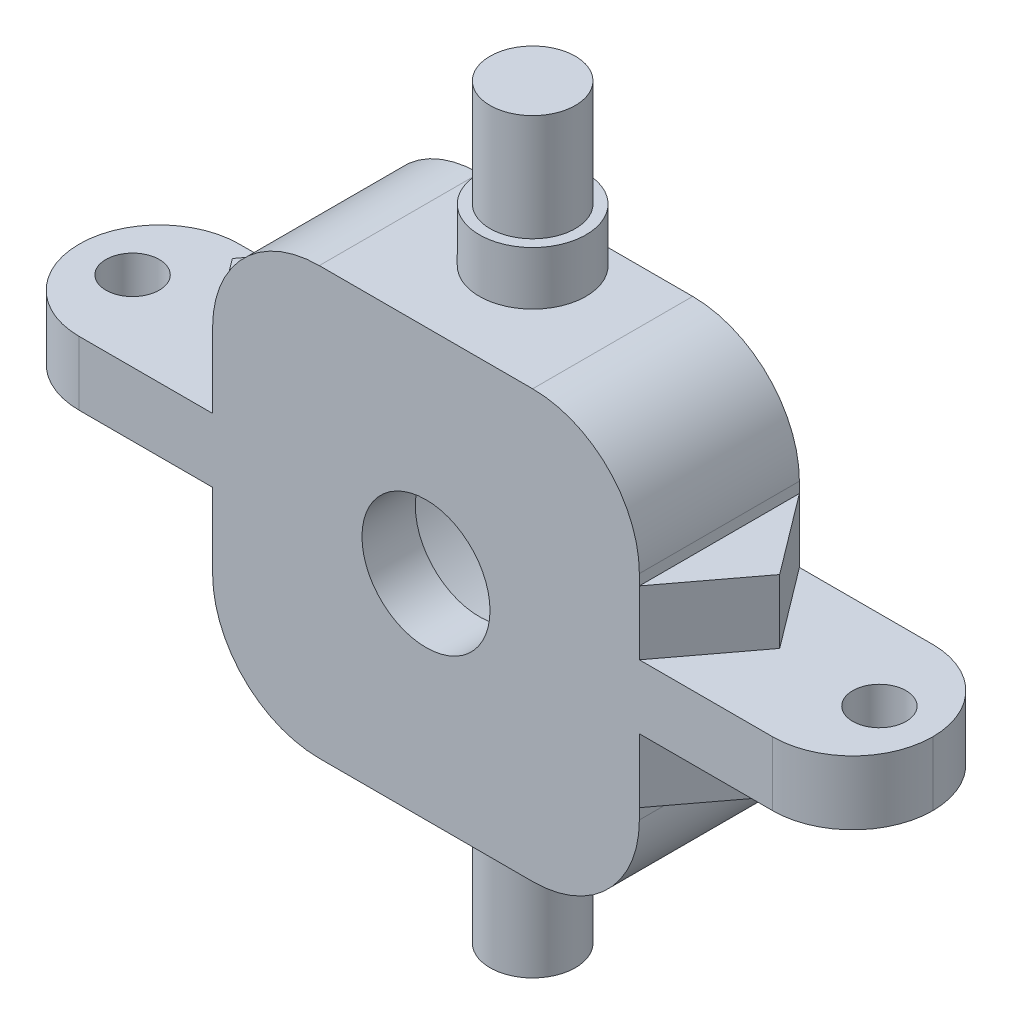
SolidWorks part; units mm, degrees
ref_plane "Front Plane" through (0, 0, 0) normal (0, 0, 1) x (1, 0, 0)
ref_plane "Top Plane" through (0, 0, 0) normal (0, 1, 0) x (1, 0, 0)
ref_plane "Right Plane" through (0, 0, 0) normal (1, 0, 0) x (0, 0, -1)
sketch "Sketch1" plane through (0, 0, 0) normal (0, 0, 1) x (1, 0, 0)
  line L1 (40, 40) -> (0, 40)
  line L2 (40, 40) -> (40, 0)
  line L3 (40, 0) -> (0, 0)
  line L4 (0, 40) -> (0, 0)
  circle A0 centre (20, 20) radius 6
  dimension "D3" = 12
  dimension "D1" = 40
  dimension "D2" = 40
extrude "Boss-Extrude1" add sketch "Sketch1" along normal blind 15
sketch "Sketch2" plane through (0, 0, 0) normal (0, 0, -1) x (-1, 0, 0)
  circle A0 centre (-20, 20) radius 15
  dimension "D1" = 30
extrude "Cut-Extrude1" cut sketch "Sketch2" against normal blind 10
sketch "Sketch4" plane through (0, 40, 0) normal (0, 1, 0) x (1, 0, 0)
  line L0 (40, 0) -> (0, 0) construction
  circle A0 centre (20, -5) radius 4
  dimension "D1" = 8
  dimension "D2" = 5
extrude "Boss-Extrude2" add sketch "Sketch4" along normal blind 15
sketch "Sketch5" plane through (0, 40, 0) normal (0, 1, 0) x (1, 0, 0)
  circle A0 centre (20, -5) radius 5
extrude "Boss-Extrude3" add sketch "Sketch5" along normal blind 5
sketch "Sketch7" plane through (0, 0, 0) normal (0, -1, 0) x (1, 0, 0)
  line L0 (0, 0) -> (40, 0) construction
  circle A0 centre (20, 5) radius 5
  dimension "D1" = 5
extrude "Boss-Extrude4" add sketch "Sketch7" along normal blind 5
sketch "Sketch8" plane through (0, -5, 0) normal (0, -1, 0) x (1, 0, 0)
  circle A0 centre (20, 5) radius 4
extrude "Boss-Extrude5" add sketch "Sketch8" along normal blind 10
fillet "Fillet1" radius 10 4 edges at (0, 40, 7.5) (0, 0, 7.5) (40, 0, 7.5) (40, 40, 7.5)
sketch "Sketch9" plane through (40, 0, 0) normal (1, 0, 0) x (0, 0, -1)
  line L0 (-15, 20) -> (0, 20) construction
  line L1 (-15, 10) -> (-15, 30) construction
  line L2 (0, 10) -> (0, 30) construction
  line L4 (-15, 17) -> (0, 17)
  line L5 (-15, 17) -> (-15, 23)
  line L6 (-15, 23) -> (0, 23)
  line L7 (0, 17) -> (0, 23)
  line L8 (-15, 17) -> (0, 23) construction
  line L9 (-15, 23) -> (0, 17) construction
  point P6 (-7.5, 20)
  dimension "D1" = 6
extrude "Boss-Extrude6" add sketch "Sketch9" along normal blind 20
sketch "Sketch10" plane through (0, 0, 0) normal (-1, 0, 0) x (0, 0, 1)
  line L1 (0, 17) -> (15, 17)
  line L2 (0, 17) -> (0, 23)
  line L3 (0, 23) -> (15, 23)
  line L4 (15, 17) -> (15, 23)
extrude "Boss-Extrude7" add sketch "Sketch10" along normal blind 20
sketch "Sketch11" plane through (0, 23, 0) normal (0, 1, 0) x (1, 0, 0)
  line L0 (50, 0) -> (50, -15) construction
  line L1 (60, 0) -> (40, 0) construction
  line L2 (60, -15) -> (40, -15) construction
  line L3 (60, 0) -> (60, -15) construction
  line L5 (-20, -15) -> (0, -15) construction
  line L10 (-20, -15) -> (-20, 0) construction
  circle A0 centre (-15, -7.5) radius 2.5
  circle A1 centre (55, -7.5) radius 2.5
  point P8 (0, 0)
  point P17 (-20, -8.5282)
  dimension "D1" = 5
  dimension "D2" = 5
  dimension "D6" = 5
  dimension "D3" = 7.5
  dimension "D4" = 7.5
  dimension "D5" = 5
extrude "Cut-Extrude2" cut sketch "Sketch11" against normal up to next
fillet "Fillet2" radius 7.5 4 edges at (-20, 20, 15) (-20, 20, 0) (60, 20, 15) (60, 20, 0)
sketch "Sketch12" plane through (0, 23, 0) normal (0, 1, 0) x (1, 0, 0)
  line L2 (0, 0) -> (0, -15)
  line L3 (0, -7.5) -> (-20, -7.5) construction
  line L4 (0, 0) -> (-5.6517, -7.5)
  line L5 (-5.6517, -7.5) -> (0, -15)
  line L6 (20, -15) -> (20, 0) construction
  line L7 (30, -15) -> (10, -15) construction
  line L8 (45.6517, -7.5) -> (40, -15)
  line L9 (40, 0) -> (45.6517, -7.5)
  line L10 (40, 0) -> (40, -15)
  circle A0 centre (20, -5) radius 5 construction
  dimension "D1" = 37
extrude "Boss-Extrude8" add sketch "Sketch12" along normal blind 6
sketch "Sketch13" plane through (0, 17, 0) normal (0, -1, 0) x (1, 0, 0)
  line L0 (0, 15) -> (-5.6517, 7.5)
  line L1 (-5.6517, 7.5) -> (0, 0)
  line L2 (0, 0) -> (0, 15)
  line L3 (40, 15) -> (45.6517, 7.5)
  line L4 (45.6517, 7.5) -> (40, 0)
  line L5 (40, 0) -> (40, 15)
extrude "Boss-Extrude9" add sketch "Sketch13" along normal blind 6
